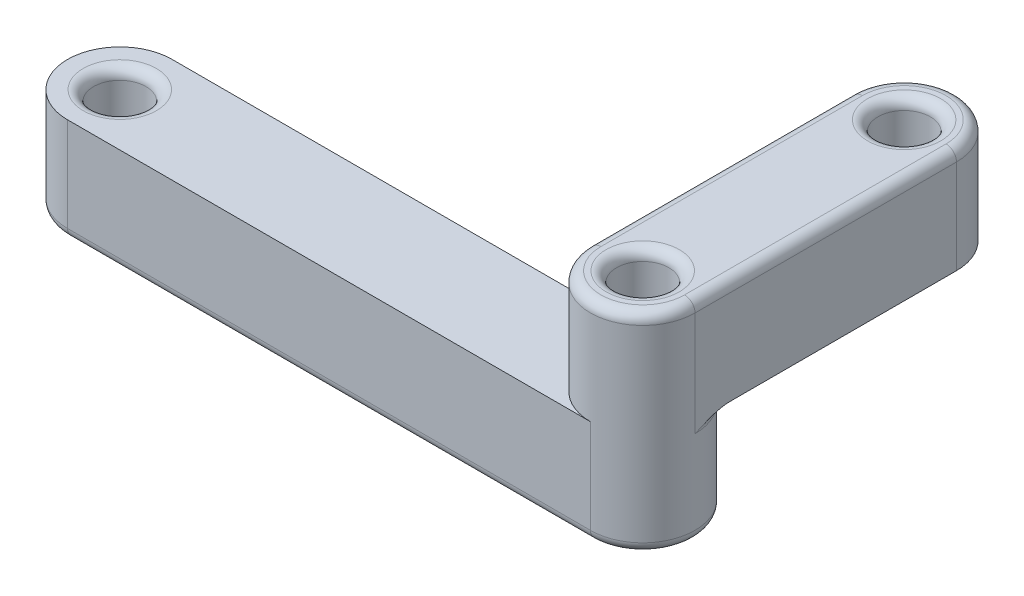
SolidWorks part; units mm, degrees
ref_plane "Front Plane" through (0, 0, 0) normal (0, 0, 1) x (1, 0, 0)
ref_plane "Top Plane" through (0, 0, 0) normal (0, 1, 0) x (1, 0, 0)
ref_plane "Right Plane" through (0, 0, 0) normal (1, 0, 0) x (0, 0, -1)
sketch "Sketch1" plane through (0, 0, 0) normal (0, 1, 0) x (1, 0, 0)
  line L0 (0, 0) -> (50, 0) construction
  line L1 (0, 5) -> (50, 5)
  line L2 (0, -5) -> (50, -5)
  arc A0 (0, 5) -> (0, -5) centre (0, 0) ccw
  arc A1 (50, -5) -> (50, 5) centre (50, 0) ccw
  circle A2 centre (0, 0) radius 2.5
  circle A3 centre (50, 0) radius 2.5
  point P3 (25, 0)
  dimension "D1" = 5
  dimension "D3" = 5
  dimension "D4" = 5
  dimension "D2" = 50
extrude "Boss-Extrude1" add sketch "Sketch1" along normal blind 10
sketch "Sketch2" plane through (0, 10, 0) normal (0, 1, 0) x (1, 0, 0)
  line L0 (50, 0) -> (50, 25) construction
  line L1 (45, 0) -> (45, 25)
  line L2 (55, 0) -> (55, 25)
  arc A0 (45, 0) -> (55, 0) centre (50, 0) ccw
  arc A1 (55, 25) -> (45, 25) centre (50, 25) ccw
  circle A2 centre (50, 0) radius 2.5
  circle A3 centre (50, 25) radius 2.5
  point P3 (50, 12.5)
  dimension "D1" = 5
  dimension "D3" = 5
  dimension "D2" = 25
extrude "Boss-Extrude2" add sketch "Sketch2" along normal blind 10
fillet "Fillet2" radius 1 16 edges at (47.5, 10, -5) (50, 0, 2.5) (0, 0, 2.5) (25, 0, 5) (55, 0, 0) (25, 0, -5) (-5, 0, 0) (0, 10, 2.5) (50, 20, 2.5) (50, 20, -22.5) (50, 10, -22.5) (53.5355, 10, -3.5355) (45, 20, -12.5) (50, 20, -30) (55, 20, -12.5) (50, 20, 5)
